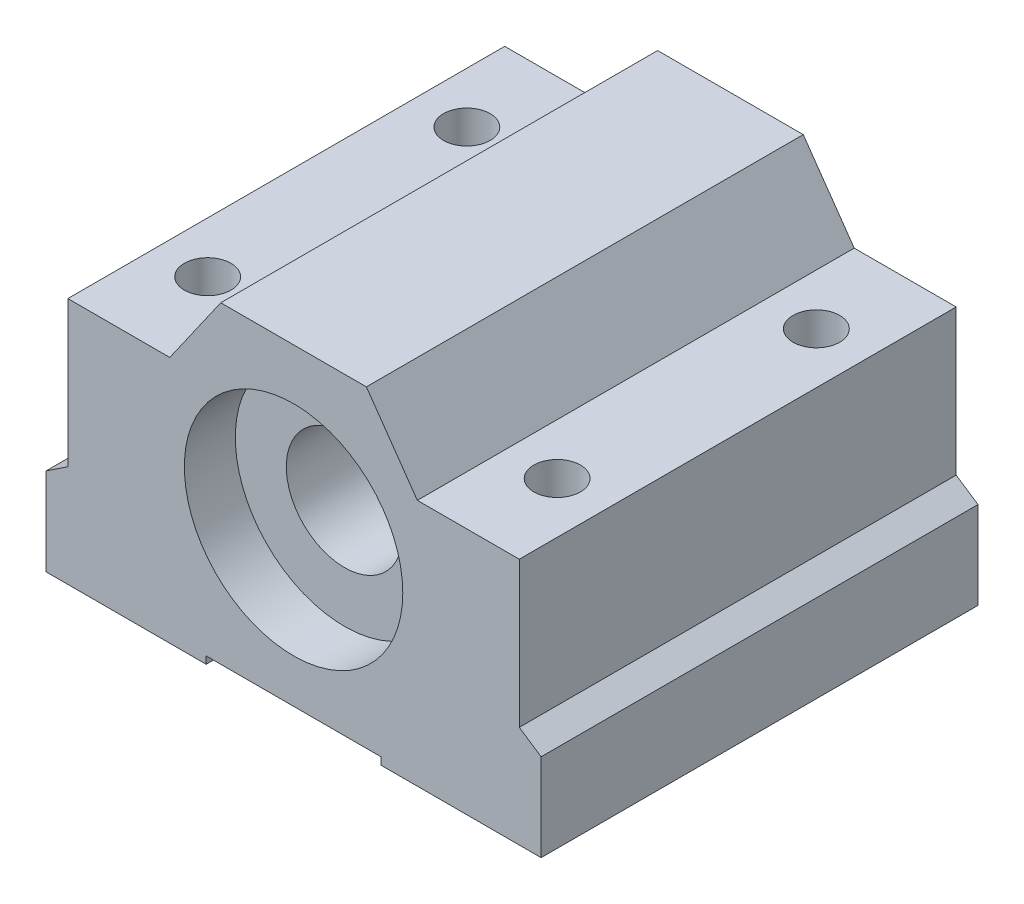
SolidWorks part; units mm, degrees
material "Alümin"
ref_plane "Ön Düzlem" through (0, 0, 0) normal (0, 0, 1) x (1, 0, 0)
ref_plane "Üst Düzlem" through (0, 0, 0) normal (0, 1, 0) x (1, 0, 0)
ref_plane "Sağ Düzlem" through (0, 0, 0) normal (1, 0, 0) x (0, 0, -1)
sketch "Çizim1" plane through (0, 0, 0) normal (0, 0, 1) x (1, 0, 0)
  line L0 (-15.5, 6) -> (-8.5, 6)
  line L2 (-17, -5) -> (-17, -11)
  line L3 (-17, -11) -> (-6, -11)
  line L4 (17, -5) -> (17, -11)
  line L5 (-17, 11) -> (17, -11) construction
  line L6 (-17, -11) -> (17, 11) construction
  line L7 (0, 11) -> (0, -11) construction
  line L8 (-6, -11) -> (-6, -10.5) construction
  line L9 (15.5, 6) -> (15.5, -4)
  line L10 (8.5, 6) -> (15.5, 6)
  line L11 (6, -11) -> (6, -10.5) construction
  line L12 (6, -11) -> (17, -11)
  line L13 (8.5, 6) -> (8.5, -5) construction
  line L14 (-8.5, 6) -> (-8.5, -5) construction
  line L15 (-5, 11) -> (-8.5, 6)
  line L16 (5, 11) -> (8.5, 6)
  line L17 (-17, -4) -> (17, -4) construction
  line L18 (-17, -5) -> (-15.5, -4)
  line L19 (17, -5) -> (15.5, -4)
  line L20 (-15.5, 6) -> (-15.5, -4)
  line L21 (-5, 11) -> (5, 11)
  line L22 (-6, -10.5) -> (6, -10.5)
  line L23 (-6, -10.5) -> (-6, -11)
  line L25 (6, -10.5) -> (6, -11)
  point P0 (0, 0)
  dimension "D1" = 34
  dimension "D2" = 22
  dimension "D3" = 17
  dimension "D4" = 0.5
  dimension "D5" = 6
  dimension "D8" = 10
extrude "Yükseklik-Ekstrüzyon1" add sketch "Çizim1" along normal blind 15 and the other way blind 15
sketch "Çizim2" plane through (0, 0, 15) normal (0, 0, 1) x (1, 0, 0)
  line L0 (0, 11) -> (0, -10.5) construction
  line L1 (5, 11) -> (-5, 11) construction
  line L2 (-6, -10.5) -> (6, -10.5) construction
  circle A0 centre (0, 0) radius 7.5
  dimension "D1" = 15
  dimension "D2" = 10.5
extrude "Kes-Ekstrüzyon1" cut sketch "Çizim2" against normal through all
ref_plane "Düzlem1" through (0, 0, 0) normal (0, 0, 1) x (1, 0, 0)
sketch "Çizim3" plane through (0, 0, 0) normal (0, 0, 1) x (1, 0, 0)
  circle A0 centre (0, 0) radius 7.5
  circle A1 centre (0, 0) radius 4
  dimension "D1" = 8
extrude "Yükseklik-Ekstrüzyon2" add sketch "Çizim3" along normal blind 11.5 and the other way blind 11.5
sketch "Çizim4" plane through (0, 6, 0) normal (0, 1, 0) x (1, 0, 0)
  line L0 (-12, 15) -> (-12, -15) construction
  line L1 (-8.5, 15) -> (-15.5, 15) construction
  line L2 (-8.5, -15) -> (-15.5, -15) construction
  line L3 (0, 15) -> (0, -15) construction
  line L4 (5, 15) -> (-5, 15) construction
  line L5 (5, -15) -> (-5, -15) construction
  circle A0 centre (-12, 8.9) radius 1.6
  circle A1 centre (-12, -8.9) radius 1.6
  circle A2 centre (12, -8.9) radius 1.6
  circle A3 centre (12, 8.9) radius 1.6
  dimension "D1" = 3.2
  dimension "D3" = 3.2
  dimension "D4" = 6.1
  dimension "D2" = 6.1
extrude "Kes-Ekstrüzyon2" cut sketch "Çizim4" against normal through all
